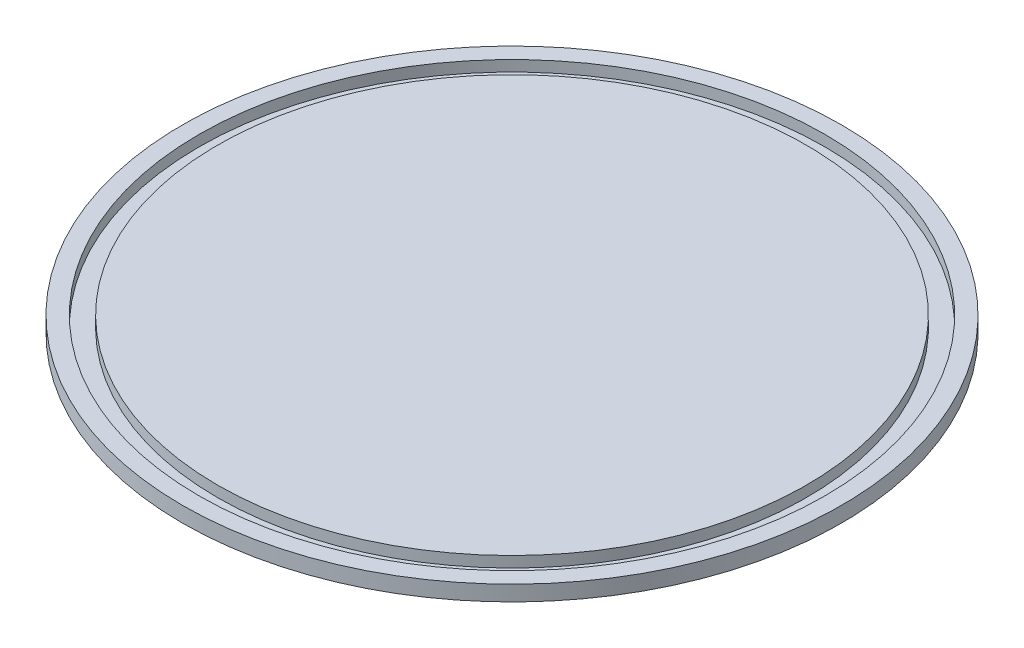
SolidWorks part; units mm, degrees
ref_plane "前基準面" through (0, 0, 0) normal (0, 0, 1) x (1, 0, 0)
ref_plane "上基準面" through (0, 0, 0) normal (0, 1, 0) x (1, 0, 0)
ref_plane "右基準面" through (0, 0, 0) normal (1, 0, 0) x (0, 0, -1)
sketch "草圖6" plane through (0, 0, 0) normal (0, 1, 0) x (1, 0, 0)
  circle A0 centre (0, 0) radius 65
  circle A1 centre (0, 0) radius 69.1
  circle A2 centre (0, 0) radius 72.75
  dimension "D1" = 130
  dimension "D2" = 4.1
  dimension "D3" = 145.5
extrude "填料-伸長4" add sketch "草圖6" along normal blind 2.4 contours A2 A1 region at (-70.6923, 0, 0)
extrude "填料-伸長5" add sketch "草圖6<3>" along normal blind 2.4 separate body contours A0 region at (0, 0, 0)
sketch "草圖6<3>" plane through (0, 0, 0) normal (0, 1, 0) x (1, 0, 0) same geometry as "草圖6"
extrude "填料-伸長6" add sketch "草圖6<4>" against normal blind 1 contours A0 | A1 A0 | A2 A1 region at (0, 0, 0) region at (-67.1456, 0, 0) region at (-70.6923, 0, 0)
sketch "草圖6<4>" plane through (0, 0, 0) normal (0, 1, 0) x (1, 0, 0) same geometry as "草圖6"
sketch "草圖7" plane through (0, 2.4, 0) normal (0, 1, 0) x (1, 0, 0)
  line L1 (-34, 34) -> (34, 34)
  line L2 (-34, 34) -> (-34, -34)
  line L3 (-34, -34) -> (34, -34)
  line L4 (34, 34) -> (34, -34)
  line L5 (-34, 34) -> (34, -34) construction
  line L6 (-34, -34) -> (34, 34) construction
  point P0 (0, 0)
  point P5 (-30, 30)
  point P10 (30, 30)
  point P11 (30, -30)
  point P12 (-30, -30)
  point P13 (0, 0)
  dimension "D1" = 68
  dimension "D2" = 4
  dimension "D3" = 4
